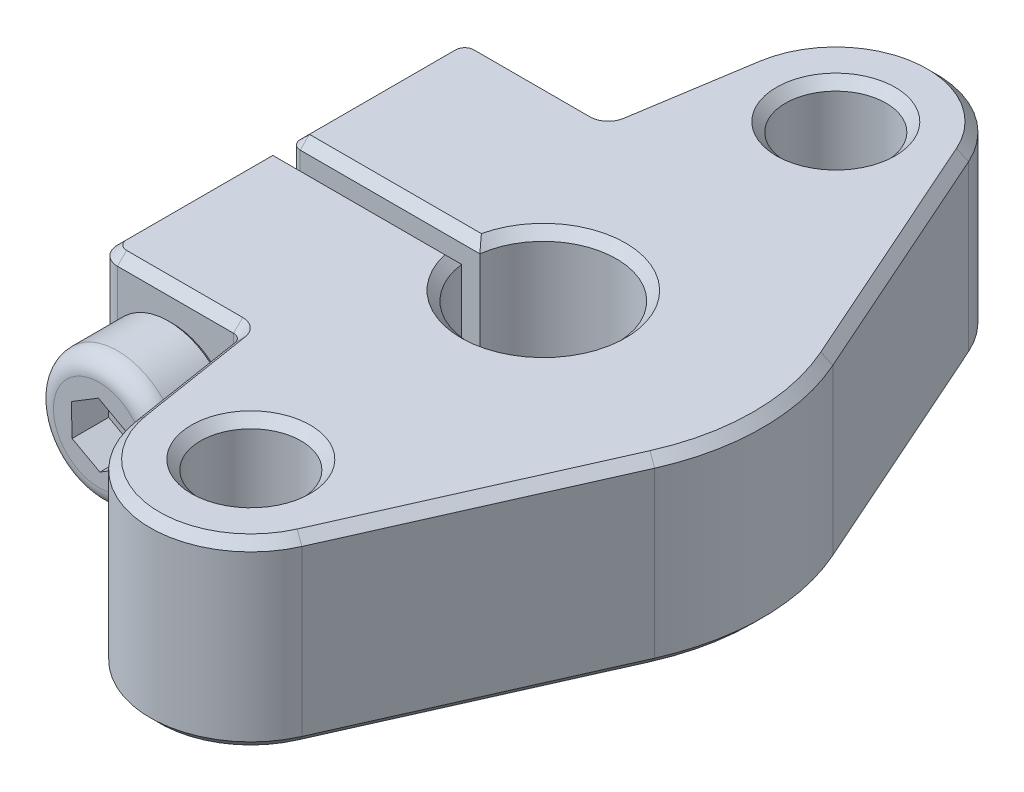
SolidWorks part; units mm, degrees
ref_plane "前视基准面" through (0, 0, 0) normal (0, 0, 1) x (1, 0, 0)
ref_plane "上视基准面" through (0, 0, 0) normal (0, 1, 0) x (1, 0, 0)
ref_plane "右视基准面" through (0, 0, 0) normal (1, 0, 0) x (0, 0, -1)
sketch "草图1" plane through (0, 0, 0) normal (0, 1, 0) x (1, 0, 0)
  line L0 (-12.1257, 0) -> (12, 0) construction
  line L1 (0, 18.2531) -> (0, -17.0921) construction
  line L2 (-12.1257, -16) -> (12, -16) construction
  line L3 (-12.1257, 16) -> (12, 16) construction
  line L4 (5.0257, -18.2344) -> (10.9651, -4.875)
  line L5 (-14.2966, -10) -> (-2.9072, -10)
  line L6 (5.0257, 18.2344) -> (10.9651, 4.875)
  line L7 (-14.2966, 10) -> (-2.9072, 10)
  line L8 (-14.2966, 0) -> (-2.9072, 0)
  line L9 (-14.2966, -0.5) -> (-2.9072, -0.5)
  line L10 (-14.2966, 0.5) -> (-2.9072, 0.5)
  line L11 (-14.2966, 0.5) -> (-14.2966, -0.5)
  line L12 (-2.9072, 0.5) -> (-2.9072, -0.5)
  line L13 (-14.2966, 10) -> (-14.2966, 0.5)
  line L14 (-14.2966, -0.5) -> (-14.2966, -10)
  line L15 (-5.4324, 16.8594) -> (-7.9017, 1.25)
  line L16 (-5.4324, -16.8594) -> (-7.9017, -1.25)
  circle A0 centre (0, 0) radius 4
  circle A1 centre (0, 16) radius 2.75
  circle A2 centre (0, -16) radius 2.75
  circle A3 centre (0, 16) radius 5.5
  circle A4 centre (0, -16) radius 5.5
  circle A5 centre (0, 0) radius 12
  circle A6 centre (0, 0) radius 8
  dimension "D1" = 8
  dimension "D4" = 5.5
  dimension "D5" = 5.5
  dimension "D6" = 11
  dimension "D7" = 11
  dimension "D10" = 24
  dimension "D13" = 16
  dimension "D11" = 10
  dimension "D8" = 0.5
  dimension "D2" = 16
  dimension "D3" = 16
  dimension "D9" = 0.5
  dimension "D12" = 10
extrude "凸台-拉伸1" add sketch "草图1" along normal blind 10 contours A6 L10 A0 L9 | A6 L16 A5 A4 A3 L15 | A5 L6 A3 | A5 A3 A1 | A5 A3 L15 | A5 L7 L13 L10 | A6 L15 L7 A5 L10 | A5 L9 L14 L5 | A6 L9 A5 L5 L16 | A5 L16 A4 | A5 A4 A2 | A5 A4 L4 | A3 A5 | A4 A5 region at (6.5539, 0, 11.8265) region at (-0.6976, 0, 21.306) region at (7.6486, 0, 8.8472) region at (-5.261, 0, 12.3489) region at (0, 0, 11.3063) region at (6.5539, 0, -11.8265) region at (-9.1413, 0, 4.3368) region at (-12.0226, 0, 6.2518) region at (5.2351, 0, -17.1113) region at (0, 0, -11.3063) region at (-7.7271, 0, 0.8512) region at (-5.261, 0, -12.3489) region at (-9.1413, 0, -4.3368) region at (-12.0226, 0, -6.2518)
sketch "草图3" plane through (0, 0, 10) normal (0, 0, 1) x (1, 0, 0)
  line L0 (-14.2966, 5) -> (-1.8681, 5) construction
  line L1 (-14.2966, 10) -> (-14.2966, 0) construction
  line L2 (-14.2966, 10) -> (-14.2966, 0) construction
  line L3 (-10.2966, 10) -> (-10.2966, 0) construction
  circle A0 centre (-10.2966, 5) radius 1.65
  circle A1 centre (-10.2966, 5) radius 2.25
  dimension "D2" = 3.3
  dimension "D3" = 4.5
  dimension "D1" = 4
extrude "切除-拉伸1" cut sketch "草图3" against normal up to next contours A1
extrude "切除-拉伸2" cut sketch "草图3<3>" against normal through all contours A0
sketch "草图3<3>" plane through (0, 0, 10) normal (0, 0, 1) x (1, 0, 0) same geometry as "草图3"
fillet "圆角1" radius 1 2 edges at (-14.2966, 5, -10) (-14.2966, 5, 10)
fillet "圆角2" radius 0.5 4 edges at (-6.5176, 5, 10) (-14.2966, 5, -0.5) (-14.2966, 5, 0.5) (-6.5176, 5, -10)
chamfer "倒角1" distance 0.5 angle 45 44 edges at (0, 10, 18.75) (0, 10, -13.25) (-14.0037, 10, -9.7071) (-10.1206, 10, -10) (-6.6199, 10, -10.1198) (-5.9416, 10, -13.6406) (-0.717, 10, -21.4531) (7.9954, 10, -11.5547) (12, 10, 0) (7.9954, 10, 11.5547) (-0.717, 10, 21.4531) (-5.9416, 10, 13.6406) (-6.6199, 10, 10.1198) (-10.1206, 10, 10) (-14.0037, 10, 9.7071) (-14.2966, 10, 5) (-14.1502, 10, 0.6464) (-8.8826, 10, 0.5) (4, 10, 0) (-8.8826, 10, -0.5) (-14.1502, 10, -0.6464) (-14.2966, 10, -5) (0, 0, 18.75) (0, 0, -13.25) (4, 0, 0) (-8.8826, 0, 0.5) (-14.1502, 0, 0.6464) (-14.2966, 0, 5) (-14.0037, 0, 9.7071) (-10.1206, 0, 10) (-6.6199, 0, 10.1198) (-5.9416, 0, 13.6406) (-0.717, 0, 21.4531) (7.9954, 0, 11.5547) (12, 0, 0) (7.9954, 0, -11.5547) (-0.717, 0, -21.4531) (-5.9416, 0, -13.6406) (-6.6199, 0, -10.1198) (-10.1206, 0, -10) (-14.0037, 0, -9.7071) (-14.2966, 0, -5) (-14.1502, 0, -0.6464) (-8.8826, 0, -0.5)
sketch "草图4" plane through (0, 0, 10) normal (0, 0, 1) x (1, 0, 0)
  circle A0 centre (-10.2966, 5) radius 3.5
  dimension "D1" = 7
extrude "凸台-拉伸2" add sketch "草图4" along normal blind 4 separate body
fillet "圆角3" radius 1 1 edges at (-6.7966, 5, 14)
sketch "草图5" plane through (0, 0, 14) normal (0, 0, 1) x (1, 0, 0)
  line L1 (-8.8174, 5.9011) -> (-10.3373, 6.7316)
  line L2 (-10.3373, 6.7316) -> (-11.8166, 5.8305)
  line L3 (-11.8166, 5.8305) -> (-11.7758, 4.0989)
  line L4 (-11.7758, 4.0989) -> (-10.2559, 3.2684)
  line L5 (-10.2559, 3.2684) -> (-8.7767, 4.1695)
  line L6 (-8.7767, 4.1695) -> (-8.8174, 5.9011)
  circle A0 centre (-10.2966, 5) radius 1.5 construction
  dimension "D1" = 3
extrude "切除-拉伸3" cut sketch "草图5" against normal blind 2
chamfer "倒角2" distance 0.2 angle 45 1 edges at (-6.7966, 5, 10)
sketch "草图6" plane through (0, 0, 10) normal (0, 0, 1) x (1, 0, 0)
  circle A0 centre (-10.2966, 5) radius 2
  dimension "D1" = 4
extrude "凸台-拉伸3" add sketch "草图6" against normal blind 16 separate body
